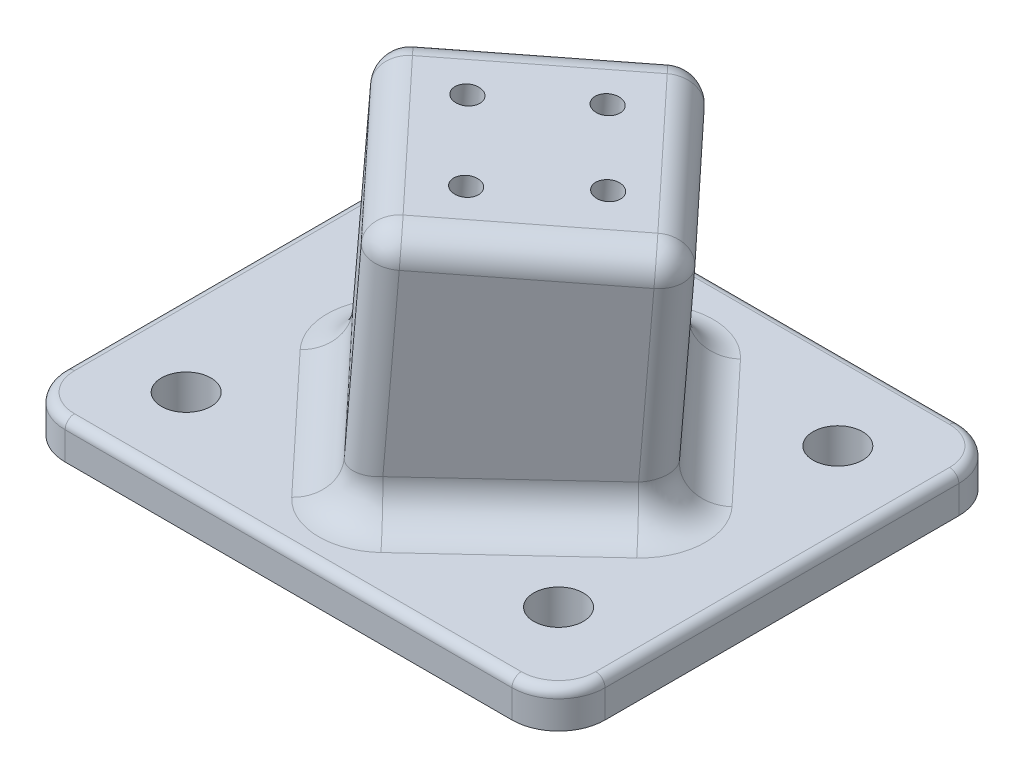
SolidWorks part; units mm, degrees
ref_plane "Front Plane" through (0, 0, 0) normal (0, 0, 1) x (1, 0, 0)
ref_plane "Top Plane" through (0, 0, 0) normal (0, 1, 0) x (1, 0, 0)
ref_plane "Right Plane" through (0, 0, 0) normal (1, 0, 0) x (0, 0, -1)
sketch "Sketch1" plane through (0, 0, 0) normal (0, 1, 0) x (1, 0, 0)
  line L1 (0, 0) -> (63.5, 0)
  line L2 (0, 0) -> (0, -50.8)
  line L3 (0, -50.8) -> (63.5, -50.8)
  line L4 (63.5, 0) -> (63.5, -50.8)
  dimension "D1" = 63.5
  dimension "D2" = 50.8
extrude "Boss-Extrude1" add sketch "Sketch1" along normal blind 5.08
ref_plane "Plane2" through (0.4824, 5.5133, 0) normal (-0.0872, -0.9962, 0) x (0, 0, -1)
sketch "Sketch2" plane through (0, 5.08, 0) normal (0, 1, 0) x (1, 0, 0)
  line L1 (0, 0) -> (0, -50.8) construction
  line L2 (63.5, 0) -> (0, 0) construction
  point P0 (6.35, -6.35)
  point P1 (57.15, -6.35)
  point P2 (57.15, -44.45)
  point P3 (6.35, -44.45)
  dimension "D1" = 50.8
  dimension "D2" = 38.1
  dimension "D3" = 50.8
  dimension "D4" = 38.1
  dimension "D5" = 6.35
  dimension "D6" = 6.35
sketch "Sketch5" plane through (0, 0, 0) normal (0, -1, 0) x (1, 0, 0)
  line L0 (0, 0) -> (0, 50.8) construction
  line L1 (0, 50.8) -> (63.5, 50.8)
  line L2 (0, 50.8) -> (0, 0)
  line L3 (0, 0) -> (63.5, 0)
  line L4 (63.5, 50.8) -> (63.5, 0)
  line L5 (63.5, 0) -> (0, 0) construction
  dimension "D1" = 50.8
  dimension "D2" = 63.5
  dimension "D3" = 0
  dimension "D4" = 0
hole_wizard "1/4 Clearance Hole1" positions "3DSketch2" profile "Sketch8" hole size "1/4" standard "ANSI Inch" end condition up to next
sketch3d "3DSketch2"
  point P0 (6.35, 5.08, 6.35)
  point P3 (6.35, 5.08, 44.45)
  point P6 (57.15, 5.08, 44.45)
  point P9 (57.15, 5.08, 6.35)
sketch "Sketch8" plane through (6.35, 5.08, 6.35) normal (1, 0, 0) x (0, 0, 1)
  line L0 (0, 0) -> (0, 5.08)
  line L1 (0, 5.08) -> (3.3782, 5.08)
  line L2 (3.3782, 5.08) -> (3.3782, 0)
  line L5 (3.3782, 0) -> (0, 0)
  line L11 (0, -6.35) -> (0, 107.95) construction
  dimension "Thru Hole Dia." = 6.7564
  dimension "Thru Hole Depth" = 5.08
sketch "Sketch13" plane through (0, 5.08, 0) normal (0, 1, 0) x (1, 0, 0)
  line L0 (0, 0) -> (63.5, 0)
  line L1 (63.5, 0) -> (63.5, -50.8)
  line L2 (63.5, -50.8) -> (0, -50.8)
  line L3 (0, 0) -> (0, -50.8) construction
  line L4 (0, -50.8) -> (63.5, -50.8) construction
  line L5 (0, -50.8) -> (0, 0)
  line L6 (-5.08, 5.08) -> (68.58, 5.08)
  line L7 (68.58, 5.08) -> (68.58, -55.88)
  line L8 (68.58, -55.88) -> (-5.08, -55.88)
  line L9 (-5.08, -55.88) -> (-5.08, 5.08)
  dimension "D1" = 73.66
  dimension "D2" = 60.96
  dimension "D3" = 5.08
  dimension "D4" = 5.08
extrude "Boss-Extrude3" add sketch "Sketch13" against normal blind 5.08
fillet "Fillet4" radius 1.27 4 edges at (68.58, 5.08, 25.4) (31.75, 5.08, -5.08) (31.75, 5.08, 55.88) (-5.08, 5.08, 25.4)
sketch "Sketch14" plane through (0.4824, 5.5133, 0) normal (0.0872, 0.9962, 0) x (0, 0, -1)
  line L0 (-25.4, -9.2972) -> (-48.992, -31.2971)
  line L1 (-48.992, -31.2971) -> (-26.9921, -54.8891)
  line L2 (-26.9921, -54.8891) -> (-3.4001, -32.8892)
  line L3 (-3.4001, -32.8892) -> (-25.4, -9.2972)
  line L4 (5.08, 5.0607) -> (-55.88, 5.0607) construction
  line L6 (-55.88, -67.987) -> (-55.88, 5.3927) construction
  point P6 (-25.4, 5.0607)
  point P11 (-55.88, -31.2971)
  dimension "D1" = 90
  dimension "D2" = 90
  dimension "D3" = 32.258
  dimension "D4" = 32.258
extrude "Boss-Extrude4" add sketch "Sketch14" along normal blind 37.338
sketch "Sketch16" plane through (0, 0, 0) normal (0, -1, 0) x (1, 0, 0)
  line L1 (0, 50.8) -> (63.5, 50.8)
  line L2 (0, 50.8) -> (0, 0)
  line L3 (0, 0) -> (63.5, 0)
  line L4 (63.5, 50.8) -> (63.5, 0)
sketch "Sketch18" plane through (3.7366, 42.7092, 0) normal (0.0872, 0.9962, 0) x (0.9962, -0.0872, 0)
  line L0 (32.8892, -3.4001) -> (54.8891, -26.9921) construction
  line L1 (54.8891, -26.9921) -> (31.2971, -48.992) construction
  point P0 (41.7388, -25.8463)
  point P1 (32.0932, -26.196)
  point P2 (22.4412, -25.8288)
  point P3 (32.3273, -16.544)
  point P4 (32.3273, -35.848)
  dimension "D1" = 16.129
  dimension "D2" = 16.129
  dimension "D3" = 9.652
  dimension "D4" = 9.652
  dimension "D5" = 9.652
  dimension "D6" = 9.652
hole_wizard "M3 Clearance Hole1" positions "3DSketch3" profile "Sketch19" hole size "M3" standard "ANSI Metric" end condition through all
sketch3d "3DSketch3"
  point P0 (35.9408, 39.8917, 16.544)
  point P3 (45.3166, 39.0715, 25.8463)
  point P6 (35.9408, 39.8917, 35.848)
  point P9 (26.0923, 40.7534, 25.8288)
sketch "Sketch19" plane through (35.9408, 39.8917, 16.544) normal (0, 0, 1) x (-0.9962, 0.0872, 0)
  line L0 (0, 0) -> (0, 43.3151)
  line L1 (0, 43.3151) -> (1.7, 43.3151)
  line L2 (1.7, 43.3151) -> (1.7, 0)
  line L5 (1.7, 0) -> (0, 0)
  line L11 (0, -6.35) -> (0, 107.95) construction
  dimension "Thru Hole Dia." = 3.4
  dimension "Thru Hole Depth" = 43.3151
fillet "Fillet5" radius 3.81 8 edges at (47.4587, 38.8841, 15.1961) (34.98, 22.4614, 3.4001) (24.7495, 40.8709, 14.4) (11.3878, 23.4895, 25.4) (23.9565, 40.9402, 37.196) (33.3879, 22.5308, 48.992) (46.6657, 38.9534, 37.9921) (56.98, 21.5027, 26.9921)
fillet "Fillet6" radius 6.35 8 edges at (68.208, 4.708, -4.708) (-4.708, 4.708, -4.708) (-4.708, 4.708, 55.508) (68.208, 4.708, 55.508) (68.58, 1.905, 55.88) (-5.08, 1.905, 55.88) (-5.08, 1.905, -5.08) (68.58, 1.905, -5.08)
fillet "Fillet7" radius 5.08 8 edges at (44.5013, 5.08, 15.1961) (21.6182, 5.08, 14.4) (20.8191, 5.08, 37.196) (43.7022, 5.08, 37.9921) (11.3604, 5.08, 25.4551) (31.9164, 5.08, 47.4148) (33.404, 5.08, 4.9773) (53.96, 5.08, 26.937)
sketch "Sketch23" plane through (3.7366, 42.7092, 0) normal (0.0872, 0.9962, 0) x (0.9962, -0.0872, 0)
  line L0 (32.5758, -12.3749) -> (18.272, -25.7134)
  line L1 (18.272, -25.7134) -> (31.6105, -40.0172)
  line L2 (31.6105, -40.0172) -> (45.9143, -26.6787)
  line L3 (45.9143, -26.6787) -> (32.5758, -12.3749)
extrude "Cut-Extrude2" [suppressed] cut sketch "Sketch23" along normal blind 33.02 from surface
sketch "Sketch25" plane through (0.4824, 5.5133, 0) normal (-0.0872, -0.9962, 0) x (0, 0, -1)
  line L0 (-25.4637, 45.4098) -> (-39.7675, 32.0713)
  line L1 (-39.7675, 32.0713) -> (-26.4289, 17.7675)
  line L2 (-26.4289, 17.7675) -> (-12.1251, 31.106)
  line L3 (-12.1251, 31.106) -> (-25.4637, 45.4098)
extrude "Cut-Extrude3" cut sketch "Sketch25" against normal blind 32.258 and the other way blind 32.258
fillet "Fillet8" radius 2.54 4 edges at (27.6376, 35.5188, 19.277) (28.1184, 35.4767, 33.0982) (41.887, 34.2721, 32.6156) (41.4062, 34.3142, 18.7944)
